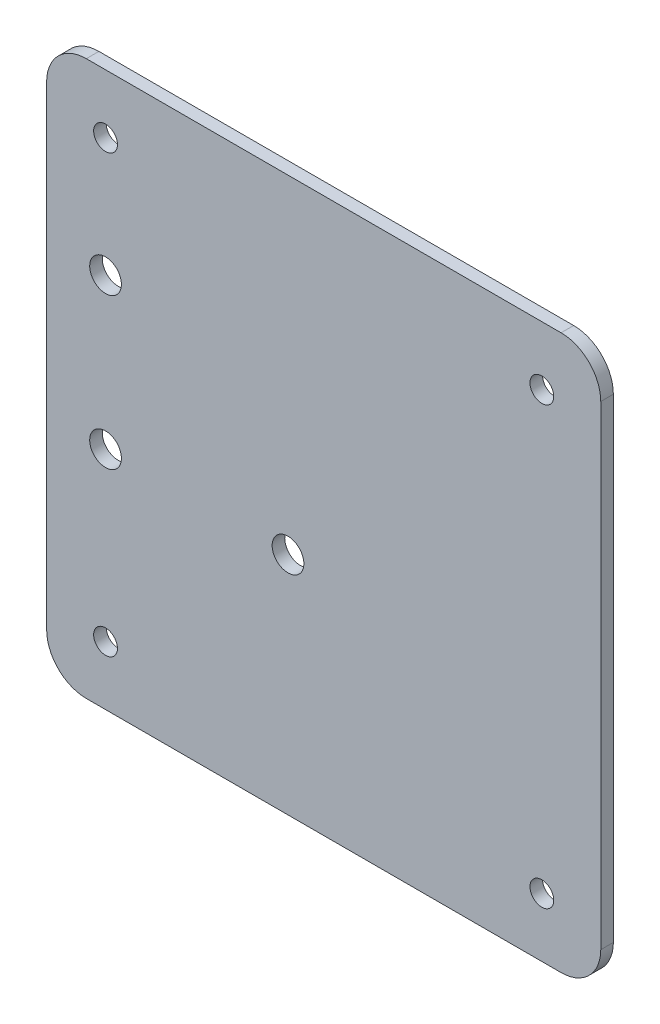
SolidWorks part; units mm, degrees
ref_plane "Front Plane" through (0, 0, 0) normal (0, 0, 1) x (1, 0, 0)
ref_plane "Top Plane" through (0, 0, 0) normal (0, 1, 0) x (1, 0, 0)
ref_plane "Right Plane" through (0, 0, 0) normal (1, 0, 0) x (0, 0, -1)
sketch "Sketch1" plane through (0, 0, 0) normal (0, 0, 1) x (1, 0, 0)
  line L0 (55.9296, 1663.3114) -> (55.9296, 1660.3114) construction
  line L1 (65.9296, 1731.72) -> (185.6296, 1731.72)
  line L2 (55.9296, 1721.72) -> (55.9296, 1602.02)
  line L3 (65.9296, 1592.02) -> (185.6296, 1592.02)
  line L4 (195.6296, 1721.72) -> (195.6296, 1602.02)
  line L5 (-98.5886, 1671.2058) -> (173.4114, 1671.2058) construction
  arc A0 (55.9296, 1602.02) -> (65.9296, 1592.02) centre (65.9296, 1602.02) ccw
  arc A1 (185.6296, 1592.02) -> (195.6296, 1602.02) centre (185.6296, 1602.02) ccw
  arc A2 (185.6296, 1731.72) -> (195.6296, 1721.72) centre (185.6296, 1721.72) cw
  arc A3 (65.9296, 1731.72) -> (55.9296, 1721.72) centre (65.9296, 1721.72) ccw
  point P10 (55.9296, 1592.02)
  point P13 (195.6296, 1592.02)
  dimension "D2" = 10
  dimension "D1" = 139.7
  dimension "D4" = 35
extrude "Boss-Extrude1" add sketch "Sketch1" along normal blind 3.175
sketch "Sketch2" plane through (0, 0, 0) normal (0, 0, -1) x (-1, 0, 0)
  line L0 (-70.7796, 1626.1374) -> (-70.7796, 1679.6302) construction
  line L1 (-116.7796, 1626.1374) -> (-116.7796, 1673.5664) construction
  line L2 (-70.7796, 1648.87) -> (-116.7796, 1648.87) construction
  line L3 (98.5886, 1671.2058) -> (-206.4114, 1671.2058) construction
  line L4 (-206.4114, 1679.2058) -> (-206.4114, 1663.2058) construction
  line L13 (-195.6296, 1661.87) -> (-55.9296, 1661.87) construction
  line L14 (-195.6296, 1602.02) -> (-195.6296, 1721.72) construction
  line L15 (-55.9296, 1721.72) -> (-55.9296, 1602.02) construction
  line L16 (-185.6296, 1731.72) -> (-65.9296, 1731.72) construction
  line L21 (-70.7796, 1606.87) -> (-70.7796, 1716.87) construction
  line L22 (-180.7796, 1606.87) -> (-70.7796, 1606.87) construction
  line L23 (-180.7796, 1716.87) -> (-180.7796, 1606.87) construction
  line L24 (-70.7796, 1716.87) -> (-180.7796, 1716.87) construction
  line L25 (-125.7796, 1731.72) -> (-125.7796, 1592.02) construction
  line L26 (-65.9296, 1592.02) -> (-185.6296, 1592.02) construction
  circle A3 centre (-70.7796, 1648.87) radius 4
  circle A4 centre (-70.7796, 1686.87) radius 4
  circle A5 centre (-116.7796, 1648.87) radius 4
  circle A6 centre (-180.7796, 1716.87) radius 3
  circle A7 centre (-70.7796, 1716.87) radius 3
  circle A8 centre (-180.7796, 1606.87) radius 3
  circle A9 centre (-70.7796, 1606.87) radius 3
  dimension "D1" = 8
  dimension "D3" = 6
  dimension "D4" = 15.6642
  dimension "D5" = 22.3358
  dimension "D6" = 9
  dimension "D7" = 46
  dimension "D8" = 55
  dimension "D2" = 55
  dimension "D9" = 55
  dimension "D10" = 55
extrude "Cut-Extrude1" cut sketch "Sketch2" against normal through all
